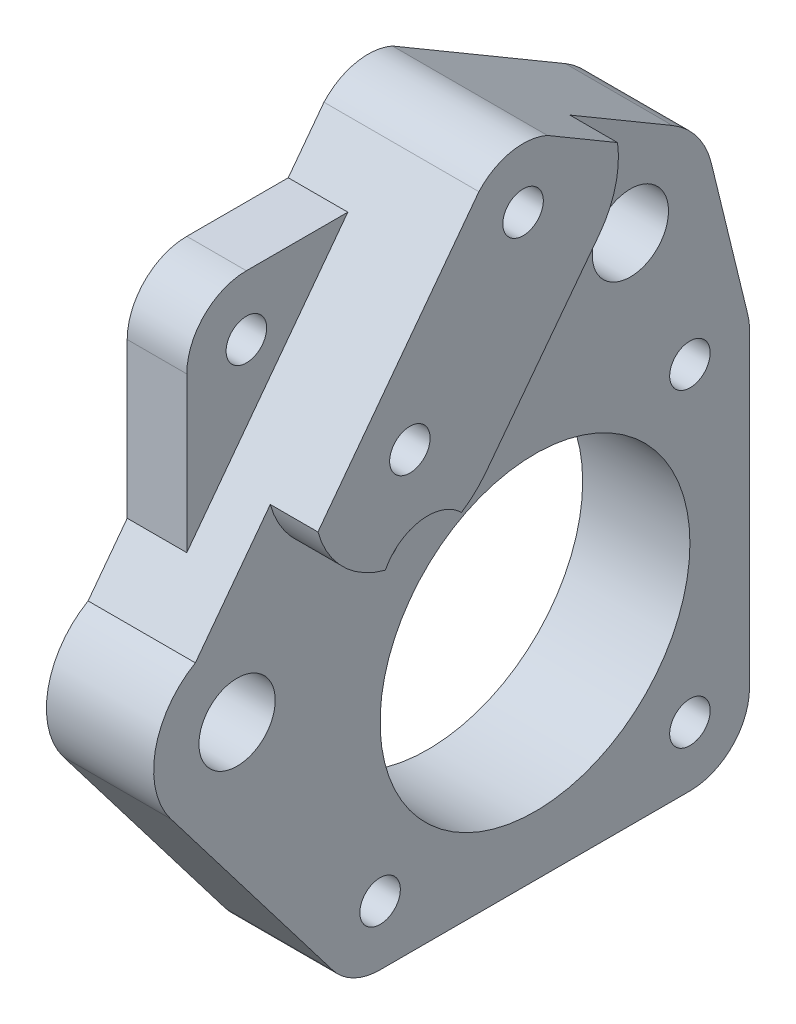
SolidWorks part; units mm, degrees
ref_plane "Front Plane" through (0, 0, 0) normal (0, 0, 1) x (1, 0, 0)
ref_plane "Top Plane" through (0, 0, 0) normal (0, 1, 0) x (1, 0, 0)
ref_plane "Right Plane" through (0, 0, 0) normal (1, 0, 0) x (0, 0, -1)
sketch "Sketch1" plane through (0, 0, 0) normal (1, 0, 0) x (0, 0, -1)
  line L0 (-16.7077, 13.3546) -> (-36.5, -12.9904)
  line L1 (-38.5623, -23.3024) -> (-23.4721, -43.0526)
  line L2 (-23.4721, -43.0526) -> (10, -43.0526)
  line L3 (10, -43.0526) -> (10, -11.4513)
  line L4 (10, -11.4513) -> (6.0989, 4.5343)
  line L5 (6.0989, 4.5343) -> (-10.96, 14.5649)
  arc A0 (-10.96, 14.5649) -> (-16.7077, 13.3546) centre (-13, 10) ccw
  arc A1 (-36.5, -12.9904) -> (-38.5623, -23.3024) centre (-33, -19.0526) ccw
extrude "Boss-Extrude1" add sketch "Sketch1" against normal blind 9
sketch "Sketch2" plane through (0, 0, 0) normal (1, 0, 0) x (0, 0, -1)
  line L0 (-30.2133, -4.6224) -> (-16.7077, 13.3546)
  line L1 (-10.96, 14.5649) -> (-5.0768, 11.1056)
  line L2 (-6.6307, 5.1593) -> (-16.1307, -7.3407)
  arc A0 (-16.1307, -7.3407) -> (-30.2133, -4.6224) centre (-22.5, -2.5) cw
  arc A1 (-16.7077, 13.3546) -> (-10.96, 14.5649) centre (-13, 10) cw
  arc A2 (-5.0768, 11.1056) -> (-6.6307, 5.1593) centre (-13, 10) cw
extrude "Boss-Extrude2" add sketch "Sketch2" along normal blind 4
sketch "Sketch3" plane through (4, 0, 0) normal (1, 0, 0) x (0, 0, -1)
  arc A0 (-24.5607, -10.23) -> (-18.1693, -9.2264) centre (-22.5, -2.5) ccw
  arc A1 (-18.1693, -9.2264) -> (-24.5607, -10.23) centre (-21, -12.0526) ccw
extrude "Cut-Extrude1" cut sketch "Sketch3" against normal blind 4
ref_plane "Plane4" through (-9, 0, 0) normal (-1, 0, 0) x (0, -1, 0)
sketch "Sketch4" plane through (-9, 0, 0) normal (-1, 0, 0) x (0, -1, 0)
  line L0 (-9.3634, 33.2193) -> (-9.3634, 19.7061)
  line L1 (-9.3634, 19.7061) -> (8.6236, 33.2193)
  line L2 (8.6236, 33.2193) -> (-9.3634, 33.2193)
extrude "Boss-Extrude3" add sketch "Sketch4" against normal blind 5
hole_wizard "Hole1" positions "Sketch6" profile "Sketch5" legacy
sketch "Sketch6" plane through (-9, 0, 0) normal (-1, 0, 0) x (0, 0, 1)
  point P0 (28.2193, 4.3634)
sketch "Sketch5" plane through (-9, 4.3634, 28.2193) normal (0, 1, 0) x (0, 0, 1)
  line L0 (0, 0) -> (0, 13)
  line L1 (0, 13) -> (1.7, 13)
  line L2 (1.7, 13) -> (1.7, 0)
  line L3 (1.7, 0) -> (0, 0)
  line L4 (0, 110) -> (0, -10) construction
  dimension "Diameter" = 3.4
  dimension "Depth" = 13
hole_wizard "Hole2" positions "Sketch8" profile "Sketch7" legacy
sketch "Sketch8" plane through (4, 0, 0) normal (1, 0, 0) x (0, 0, -1)
  point P0 (-13, 10)
sketch "Sketch7" plane through (4, 10, 13) normal (0, 1, 0) x (0, 0, -1)
  line L0 (0, 0) -> (0, 13)
  line L1 (0, 13) -> (1.7, 13)
  line L2 (1.7, 13) -> (1.7, 0)
  line L3 (1.7, 0) -> (0, 0)
  line L4 (0, 110) -> (0, -10) construction
  dimension "Diameter" = 3.4
  dimension "Depth" = 13
hole_wizard "Hole3" positions "Sketch10" profile "Sketch9" legacy
sketch "Sketch10" plane through (4, 0, 0) normal (1, 0, 0) x (0, 0, -1)
  point P0 (-22.5, -2.5)
sketch "Sketch9" plane through (4, -2.5, 22.5) normal (0, 1, 0) x (0, 0, -1)
  line L0 (0, 0) -> (0, 13)
  line L1 (0, 13) -> (1.7, 13)
  line L2 (1.7, 13) -> (1.7, 0)
  line L3 (1.7, 0) -> (0, 0)
  line L4 (0, 110) -> (0, -10) construction
  dimension "Diameter" = 3.4
  dimension "Depth" = 13
hole_wizard "Hole4" positions "Sketch12" profile "Sketch11" legacy
sketch "Sketch12" plane through (0, 0, 0) normal (1, 0, 0) x (0, 0, -1)
  point P0 (-8, -25.0526)
sketch "Sketch11" plane through (0, -25.0526, 8) normal (0, 1, 0) x (0, 0, -1)
  line L0 (0, 0) -> (0, 9)
  line L1 (0, 9) -> (13, 9)
  line L2 (13, 9) -> (13, 0)
  line L3 (13, 0) -> (0, 0)
  line L4 (0, 110) -> (0, -10) construction
  dimension "Diameter" = 26
  dimension "Depth" = 9
hole_wizard "Hole5" positions "Sketch14" profile "Sketch13" legacy
sketch "Sketch14" plane through (0, 0, 0) normal (1, 0, 0) x (0, 0, -1)
  point P0 (5, -38.0526)
sketch "Sketch13" plane through (0, -38.0526, -5) normal (0, 1, 0) x (0, 0, -1)
  line L0 (0, 0) -> (0, 9)
  line L1 (0, 9) -> (1.7, 9)
  line L2 (1.7, 9) -> (1.7, 0)
  line L3 (1.7, 0) -> (0, 0)
  line L4 (0, 110) -> (0, -10) construction
  dimension "Diameter" = 3.4
  dimension "Depth" = 9
hole_wizard "Hole6" positions "Sketch16" profile "Sketch15" legacy
sketch "Sketch16" plane through (0, 0, 0) normal (1, 0, 0) x (0, 0, -1)
  point P0 (-21, -38.0526)
sketch "Sketch15" plane through (0, -38.0526, 21) normal (0, 1, 0) x (0, 0, -1)
  line L0 (0, 0) -> (0, 9)
  line L1 (0, 9) -> (1.7, 9)
  line L2 (1.7, 9) -> (1.7, 0)
  line L3 (1.7, 0) -> (0, 0)
  line L4 (0, 110) -> (0, -10) construction
  dimension "Diameter" = 3.4
  dimension "Depth" = 9
hole_wizard "Hole7" positions "Sketch18" profile "Sketch17" legacy
sketch "Sketch18" plane through (0, 0, 0) normal (1, 0, 0) x (0, 0, -1)
  point P0 (-21, -12.0526)
sketch "Sketch17" plane through (0, -12.0526, 21) normal (0, 1, 0) x (0, 0, -1)
  line L0 (0, 0) -> (0, 9)
  line L1 (0, 9) -> (1.7, 9)
  line L2 (1.7, 9) -> (1.7, 0)
  line L3 (1.7, 0) -> (0, 0)
  line L4 (0, 110) -> (0, -10) construction
  dimension "Diameter" = 3.4
  dimension "Depth" = 9
hole_wizard "Hole8" positions "Sketch20" profile "Sketch19" legacy
sketch "Sketch20" plane through (0, 0, 0) normal (1, 0, 0) x (0, 0, -1)
  point P0 (5, -12.0526)
sketch "Sketch19" plane through (0, -12.0526, -5) normal (0, 1, 0) x (0, 0, -1)
  line L0 (0, 0) -> (0, 9)
  line L1 (0, 9) -> (1.7, 9)
  line L2 (1.7, 9) -> (1.7, 0)
  line L3 (1.7, 0) -> (0, 0)
  line L4 (0, 110) -> (0, -10) construction
  dimension "Diameter" = 3.4
  dimension "Depth" = 9
hole_wizard "Hole9" positions "Sketch22" profile "Sketch21" legacy
sketch "Sketch22" plane through (0, 0, 0) normal (1, 0, 0) x (0, 0, -1)
  point P0 (0, 0)
sketch "Sketch21" plane through (0, 0, 0) normal (0, 1, 0) x (0, 0, -1)
  line L0 (0, 0) -> (0, 9)
  line L1 (0, 9) -> (3.2, 9)
  line L2 (3.2, 9) -> (3.2, 0)
  line L3 (3.2, 0) -> (0, 0)
  line L4 (0, 110) -> (0, -10) construction
  dimension "Diameter" = 6.4
  dimension "Depth" = 9
hole_wizard "Hole10" positions "Sketch24" profile "Sketch23" legacy
sketch "Sketch24" plane through (0, 0, 0) normal (1, 0, 0) x (0, 0, -1)
  point P0 (-33, -19.0526)
sketch "Sketch23" plane through (0, -19.0526, 33) normal (0, 1, 0) x (0, 0, -1)
  line L0 (0, 0) -> (0, 9)
  line L1 (0, 9) -> (3.2, 9)
  line L2 (3.2, 9) -> (3.2, 0)
  line L3 (3.2, 0) -> (0, 0)
  line L4 (0, 110) -> (0, -10) construction
  dimension "Diameter" = 6.4
  dimension "Depth" = 9
fillet "Fillet1" radius 5 1 edges at (-4.5, -43.0526, -10) tangent propagation no
fillet "Fillet2" radius 5 1 edges at (-4.5, -11.4513, -10) tangent propagation no
fillet "Fillet3" radius 5 1 edges at (-6.5, 9.3634, 33.2193) tangent propagation no
fillet "Fillet4" radius 5 1 edges at (-4.5, -43.0526, 23.4721) tangent propagation no
fillet "Fillet5" radius 7 1 edges at (-4.5, 4.5343, -6.0989) tangent propagation no
ref_axis "Axis1" through (-9, -19.0526, 33) along (1, 0, 0)
ref_axis "Axis2" through (-9, 0, 0) along (1, 0, 0)
ref_plane "Plane5" through (0, 0, 0) normal (0, 0.866, 0.5) x (-1, 0, 0)
